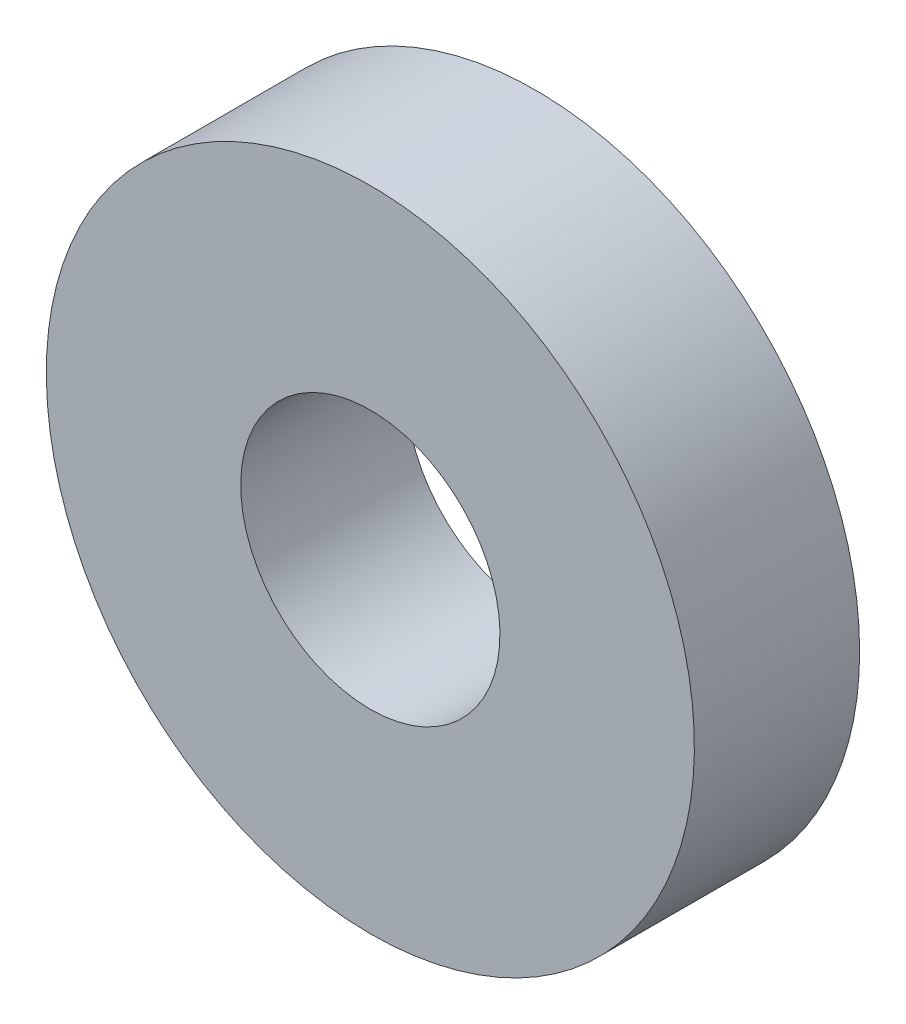
SolidWorks part; units mm, degrees
ref_plane "Front Plane" through (0, 0, 0) normal (0, 0, 1) x (1, 0, 0)
ref_plane "Top Plane" through (0, 0, 0) normal (0, 1, 0) x (1, 0, 0)
ref_plane "Right Plane" through (0, 0, 0) normal (1, 0, 0) x (0, 0, -1)
sketch "Sketch1" plane through (0, 0, 12.6) normal (0, 0, 1) x (1, 0, 0)
  circle A1 centre (-70, 14.1421) radius 3
  circle A2 centre (-70, 14.1421) radius 7.5
  arc A4 (-70.633, 21.6154) -> (-73.4637, 7.4898) centre (-70, 14.1421) ccw construction
  circle A5 centre (-70, 14.1421) radius 3 construction
extrude "Boss-Extrude1" add sketch "Sketch1" along normal up to surface (3.825 mm away)
